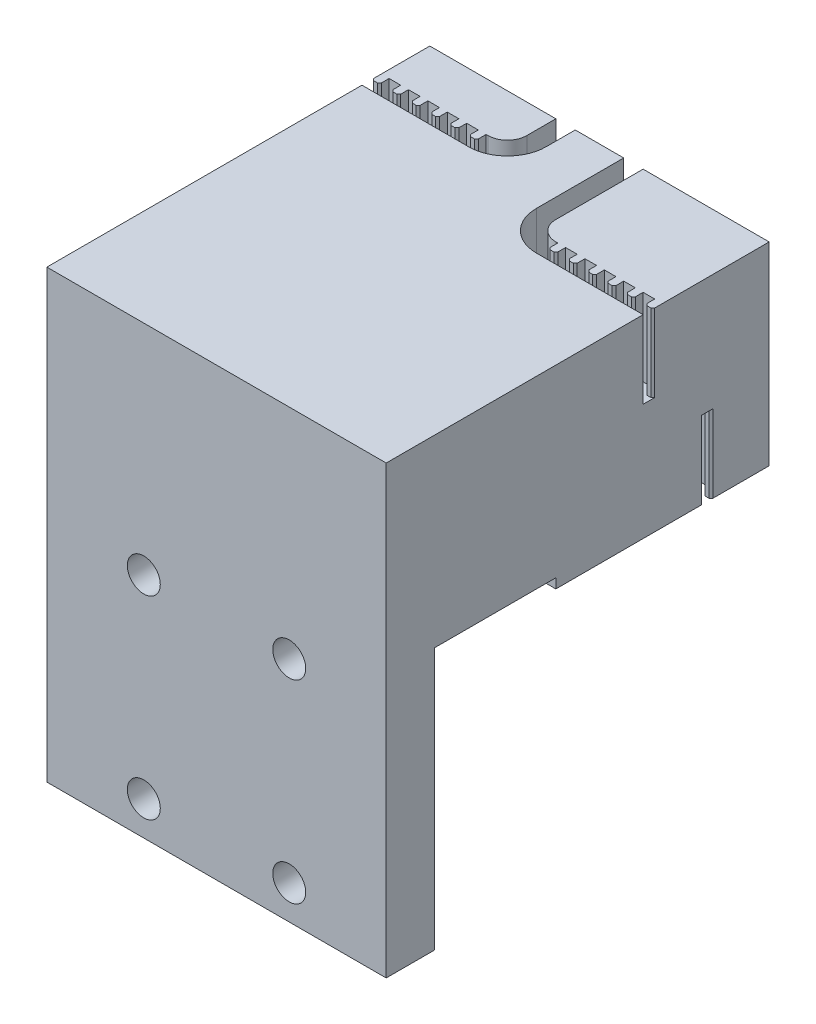
SolidWorks part; units mm, degrees
ref_plane "Front Plane" through (0, 0, 0) normal (0, 0, 1) x (1, 0, 0)
ref_plane "Top Plane" through (0, 0, 0) normal (0, 1, 0) x (1, 0, 0)
ref_plane "Right Plane" through (0, 0, 0) normal (1, 0, 0) x (0, 0, -1)
sketch "Sketch1" plane through (0, 0, 0) normal (0, 1, 0) x (1, 0, 0)
  line L1 (0, 0) -> (35, 0)
  line L2 (0, 0) -> (0, 22)
  line L3 (0, 22) -> (35, 22)
  line L4 (35, 0) -> (35, 22)
  dimension "D1" = 22
  dimension "D2" = 35
extrude "Boss-Extrude1" add sketch "Sketch1" along normal blind 20
sketch "Sketch2" plane through (0, 20, 0) normal (0, 1, 0) x (1, 0, 0)
  line L0 (0, 15) -> (11, 15)
  line L1 (0, 22) -> (0, 0) construction
  line L2 (15, 19) -> (15, 22)
  line L3 (35, 22) -> (0, 22) construction
  line L4 (0, 17) -> (11, 17)
  line L5 (13, 19) -> (13, 22)
  line L6 (35, 9) -> (24, 9)
  line L7 (35, 0) -> (35, 22) construction
  line L8 (20, 13) -> (20, 22)
  line L9 (0, 0) -> (35, 0) construction
  line L10 (22, 22) -> (22, 13)
  line L11 (24, 11) -> (35, 11)
  line L12 (35, 11) -> (35, 9)
  line L13 (0, 15) -> (0, 17)
  line L14 (13, 22) -> (15, 22)
  line L15 (20, 22) -> (22, 22)
  arc A0 (15, 19) -> (11, 15) centre (11, 19) cw
  arc A1 (13, 19) -> (11, 17) centre (11, 19) cw
  arc A2 (20, 13) -> (24, 9) centre (24, 13) ccw
  arc A3 (22, 13) -> (24, 11) centre (24, 13) ccw
  point P9 (15, 15)
  point P15 (13, 17)
  point P29 (20, 9)
  point P32 (22, 11)
  dimension "D3" = 4
  dimension "D6" = 2
  dimension "D11" = 4
  dimension "D12" = 2
  dimension "D1" = 15
  dimension "D2" = 7
  dimension "D4" = 5
  dimension "D5" = 13
  dimension "D7" = 15
  dimension "D8" = 9
  dimension "D9" = 13
  dimension "D10" = 2
extrude "Cut-Extrude1" cut sketch "Sketch2" against normal blind 8
sketch "Sketch5" plane through (0, 0, 0) normal (0, -1, 0) x (-1, 0, 0)
  line L0 (-35, 15) -> (-24, 15)
  line L2 (-20, 19) -> (-20, 22)
  line L4 (-35, 17) -> (-24, 17)
  line L5 (-22, 19) -> (-22, 22)
  line L6 (0, 9) -> (-11, 9)
  line L8 (-15, 13) -> (-15, 22)
  line L10 (-13, 22) -> (-13, 13)
  line L11 (-11, 11) -> (0, 11)
  line L12 (0, 11) -> (0, 9)
  line L13 (-35, 15) -> (-35, 17)
  line L14 (-22, 22) -> (-20, 22)
  line L15 (-15, 22) -> (-13, 22)
  line L16 (-35, 0) -> (-35, 22) construction
  line L17 (-35, 22) -> (0, 22) construction
  line L18 (0, 22) -> (0, 0) construction
  line L19 (0, 0) -> (-35, 0) construction
  arc A0 (-20, 19) -> (-24, 15) centre (-24, 19) cw
  arc A1 (-22, 19) -> (-24, 17) centre (-24, 19) cw
  arc A2 (-15, 13) -> (-11, 9) centre (-11, 13) ccw
  arc A3 (-13, 13) -> (-11, 11) centre (-11, 13) ccw
  point P9 (-20, 15)
  point P15 (-22, 17)
  point P29 (-15, 9)
  point P32 (-13, 11)
  dimension "D3" = 4
  dimension "D6" = 2
  dimension "D11" = 4
  dimension "D12" = 2
  dimension "D1" = 15
  dimension "D2" = 7
  dimension "D4" = 5
  dimension "D5" = 13
  dimension "D7" = 15
  dimension "D8" = 0
  dimension "D9" = 13
  dimension "D10" = 2
  dimension "D13" = 0
  dimension "D14" = 0
  dimension "D15" = 0
  dimension "D16" = 9
extrude "Cut-Extrude2" cut sketch "Sketch5" against normal blind 8
sketch "Sketch6" plane through (0, 20, 0) normal (0, 1, 0) x (1, 0, 0)
  line L0 (0.2, 16) -> (0, 16.2)
  line L1 (0, 17) -> (0.8, 17)
  line L2 (0, 17) -> (0, 16.2)
  line L3 (0.2, 16) -> (0.6, 16)
  line L4 (0.8, 17) -> (0.8, 16.2)
  line L5 (0.6, 16) -> (0.8, 16.2)
  line L6 (2.2, 16) -> (2, 16.2)
  line L7 (2, 17) -> (2.8, 17)
  line L8 (2, 17) -> (2, 16.2)
  line L9 (2.2, 16) -> (2.6, 16)
  line L10 (2.8, 17) -> (2.8, 16.2)
  line L11 (2.6, 16) -> (2.8, 16.2)
  line L12 (4.2, 16) -> (4, 16.2)
  line L13 (4, 17) -> (4.8, 17)
  line L14 (4, 17) -> (4, 16.2)
  line L15 (4.2, 16) -> (4.6, 16)
  line L16 (4.8, 17) -> (4.8, 16.2)
  line L17 (4.6, 16) -> (4.8, 16.2)
  line L18 (6.2, 16) -> (6, 16.2)
  line L19 (6, 17) -> (6.8, 17)
  line L20 (6, 17) -> (6, 16.2)
  line L21 (6.2, 16) -> (6.6, 16)
  line L22 (6.8, 17) -> (6.8, 16.2)
  line L23 (6.6, 16) -> (6.8, 16.2)
  line L24 (8.2, 16) -> (8, 16.2)
  line L25 (8, 17) -> (8.8, 17)
  line L26 (8, 17) -> (8, 16.2)
  line L27 (8.2, 16) -> (8.6, 16)
  line L28 (8.8, 17) -> (8.8, 16.2)
  line L29 (8.6, 16) -> (8.8, 16.2)
  line L30 (10.2, 16) -> (10, 16.2)
  line L31 (10, 17) -> (10.8, 17)
  line L32 (10, 17) -> (10, 16.2)
  line L33 (10.2, 16) -> (10.6, 16)
  line L34 (10.8, 17) -> (10.8, 16.2)
  line L35 (10.6, 16) -> (10.8, 16.2)
  line L36 (34.4, 10) -> (34.2, 10.2)
  line L37 (34.2, 11) -> (35, 11)
  line L38 (34.2, 11) -> (34.2, 10.2)
  line L39 (34.4, 10) -> (34.8, 10)
  line L40 (35, 11) -> (35, 10.2)
  line L41 (34.8, 10) -> (35, 10.2)
  line L42 (35, 11) -> (24, 11) construction
  line L43 (35, 9) -> (35, 11) construction
  line L44 (32.4, 10) -> (32.2, 10.2)
  line L45 (32.2, 11) -> (33, 11)
  line L46 (32.2, 11) -> (32.2, 10.2)
  line L47 (32.4, 10) -> (32.8, 10)
  line L48 (33, 11) -> (33, 10.2)
  line L49 (32.8, 10) -> (33, 10.2)
  line L50 (30.4, 10) -> (30.2, 10.2)
  line L51 (30.2, 11) -> (31, 11)
  line L52 (30.2, 11) -> (30.2, 10.2)
  line L53 (30.4, 10) -> (30.8, 10)
  line L54 (31, 11) -> (31, 10.2)
  line L55 (30.8, 10) -> (31, 10.2)
  line L56 (28.4, 10) -> (28.2, 10.2)
  line L57 (28.2, 11) -> (29, 11)
  line L58 (28.2, 11) -> (28.2, 10.2)
  line L59 (28.4, 10) -> (28.8, 10)
  line L60 (29, 11) -> (29, 10.2)
  line L61 (28.8, 10) -> (29, 10.2)
  line L62 (26.4, 10) -> (26.2, 10.2)
  line L63 (26.2, 11) -> (27, 11)
  line L64 (26.2, 11) -> (26.2, 10.2)
  line L65 (26.4, 10) -> (26.8, 10)
  line L66 (27, 11) -> (27, 10.2)
  line L67 (26.8, 10) -> (27, 10.2)
  line L68 (24.4, 10) -> (24.2, 10.2)
  line L69 (24.2, 11) -> (25, 11)
  line L70 (24.2, 11) -> (24.2, 10.2)
  line L71 (24.4, 10) -> (24.8, 10)
  line L72 (25, 11) -> (25, 10.2)
  line L73 (24.8, 10) -> (25, 10.2)
  dimension "D1" = 6
  dimension "D2" = 0.8
  dimension "D3" = 0.8
  dimension "D4" = 0
  dimension "D5" = 0
  dimension "D6" = 6
  dimension "D7" = 0.8
  dimension "D8" = 0.8
  dimension "D9" = 0.8
  dimension "D10" = 0.8
extrude "Boss-Extrude2" add sketch "Sketch6" against normal blind 8
sketch "Sketch8" plane through (0, 0, 0) normal (0, -1, 0) x (1, 0, 0)
  line L0 (35, -17) -> (35, -16.2)
  line L1 (35, -17) -> (35, -15) construction
  line L2 (35, -16.2) -> (34.8, -16)
  line L3 (34.8, -16) -> (34.4, -16)
  line L4 (34.4, -16) -> (34.2, -16.2)
  line L5 (34.2, -16.2) -> (34.2, -17)
  line L6 (34.2, -17) -> (35, -17)
  line L7 (33, -17) -> (33, -16.2)
  line L8 (33, -16.2) -> (32.8, -16)
  line L9 (32.8, -16) -> (32.4, -16)
  line L10 (32.4, -16) -> (32.2, -16.2)
  line L11 (32.2, -16.2) -> (32.2, -17)
  line L12 (32.2, -17) -> (33, -17)
  line L13 (31, -17) -> (31, -16.2)
  line L14 (31, -16.2) -> (30.8, -16)
  line L15 (30.8, -16) -> (30.4, -16)
  line L16 (30.4, -16) -> (30.2, -16.2)
  line L17 (30.2, -16.2) -> (30.2, -17)
  line L18 (30.2, -17) -> (31, -17)
  line L19 (29, -17) -> (29, -16.2)
  line L20 (29, -16.2) -> (28.8, -16)
  line L21 (28.8, -16) -> (28.4, -16)
  line L22 (28.4, -16) -> (28.2, -16.2)
  line L23 (28.2, -16.2) -> (28.2, -17)
  line L24 (28.2, -17) -> (29, -17)
  line L25 (27, -17) -> (27, -16.2)
  line L26 (27, -16.2) -> (26.8, -16)
  line L27 (26.8, -16) -> (26.4, -16)
  line L28 (26.4, -16) -> (26.2, -16.2)
  line L29 (26.2, -16.2) -> (26.2, -17)
  line L30 (26.2, -17) -> (27, -17)
  line L31 (25, -17) -> (25, -16.2)
  line L32 (25, -16.2) -> (24.8, -16)
  line L33 (24.8, -16) -> (24.4, -16)
  line L34 (24.4, -16) -> (24.2, -16.2)
  line L35 (24.2, -16.2) -> (24.2, -17)
  line L36 (24.2, -17) -> (25, -17)
  line L37 (0.8, -11) -> (0.8, -10.2)
  line L38 (0.8, -10.2) -> (0.6, -10)
  line L39 (0.6, -10) -> (0.2, -10)
  line L40 (0.2, -10) -> (0, -10.2)
  line L41 (0, -10.2) -> (0, -11)
  line L42 (0, -11) -> (0.8, -11)
  line L43 (0, -11) -> (11, -11) construction
  line L44 (2.8, -11) -> (2.8, -10.2)
  line L45 (2.8, -10.2) -> (2.6, -10)
  line L46 (2.6, -10) -> (2.2, -10)
  line L47 (2.2, -10) -> (2, -10.2)
  line L48 (2, -10.2) -> (2, -11)
  line L49 (2, -11) -> (2.8, -11)
  line L50 (4.8, -11) -> (4.8, -10.2)
  line L51 (4.8, -10.2) -> (4.6, -10)
  line L52 (4.6, -10) -> (4.2, -10)
  line L53 (4.2, -10) -> (4, -10.2)
  line L54 (4, -10.2) -> (4, -11)
  line L55 (4, -11) -> (4.8, -11)
  line L56 (6.8, -11) -> (6.8, -10.2)
  line L57 (6.8, -10.2) -> (6.6, -10)
  line L58 (6.6, -10) -> (6.2, -10)
  line L59 (6.2, -10) -> (6, -10.2)
  line L60 (6, -10.2) -> (6, -11)
  line L61 (6, -11) -> (6.8, -11)
  line L62 (8.8, -11) -> (8.8, -10.2)
  line L63 (8.8, -10.2) -> (8.6, -10)
  line L64 (8.6, -10) -> (8.2, -10)
  line L65 (8.2, -10) -> (8, -10.2)
  line L66 (8, -10.2) -> (8, -11)
  line L67 (8, -11) -> (8.8, -11)
  line L68 (10.8, -11) -> (10.8, -10.2)
  line L69 (10.8, -10.2) -> (10.6, -10)
  line L70 (10.6, -10) -> (10.2, -10)
  line L71 (10.2, -10) -> (10, -10.2)
  line L72 (10, -10.2) -> (10, -11)
  line L73 (10, -11) -> (10.8, -11)
  dimension "D1" = 0.8
  dimension "D2" = 0.2
  dimension "D3" = 0.8
  dimension "D4" = 0.8
  dimension "D5" = 0.2
  dimension "D6" = 6
  dimension "D7" = 0.8
  dimension "D8" = 0.2
  dimension "D9" = 0.8
  dimension "D10" = 0.8
  dimension "D11" = 0.2
  dimension "D12" = 0
  dimension "D13" = 0
  dimension "D14" = 6
extrude "Boss-Extrude4" add sketch "Sketch8" against normal blind 8
sketch "Sketch9" plane through (0, 0, 0) normal (0, 0, 1) x (1, 0, 0)
  line L1 (0, 20) -> (35, 20)
  line L2 (0, 20) -> (0, 1)
  line L3 (0, 1) -> (35, 1)
  line L4 (35, 20) -> (35, 1)
  line L5 (35, 20) -> (35, 0) construction
  dimension "D1" = 19
  dimension "D2" = 35
extrude "Boss-Extrude5" add sketch "Sketch9" along normal blind 12.5
sketch "Sketch11" plane through (0, 0, 12.5) normal (0, 0, 1) x (1, 0, 0)
  line L1 (0, 20) -> (35, 20)
  line L2 (0, 20) -> (0, -26)
  line L3 (0, -26) -> (35, -26)
  line L4 (35, 20) -> (35, -26)
  dimension "D1" = 46
  dimension "D2" = 35
extrude "Boss-Extrude6" add sketch "Sketch11" along normal blind 5
sketch "Sketch12" plane through (0, 0, 17.5) normal (0, 0, 1) x (1, 0, 0)
  line L0 (0, 20) -> (0, -26) construction
  line L1 (0, -26) -> (35, -26) construction
  line L3 (35, 20) -> (0, 20) construction
  circle A0 centre (10, -2.5) radius 1.7
  circle A1 centre (25, -2.5) radius 1.7
  circle A2 centre (25, -22.5) radius 1.7
  circle A3 centre (10, -22.5) radius 1.7
  point P0 (17.5, -12.5)
  dimension "D3" = 3.4
  dimension "D4" = 7.5
  dimension "D1" = 17.5
  dimension "D2" = 13.5
  dimension "D5" = 10
  dimension "D7" = 46
  dimension "D6" = 2
extrude "Cut-Extrude3" cut sketch "Sketch12" against normal blind 5
